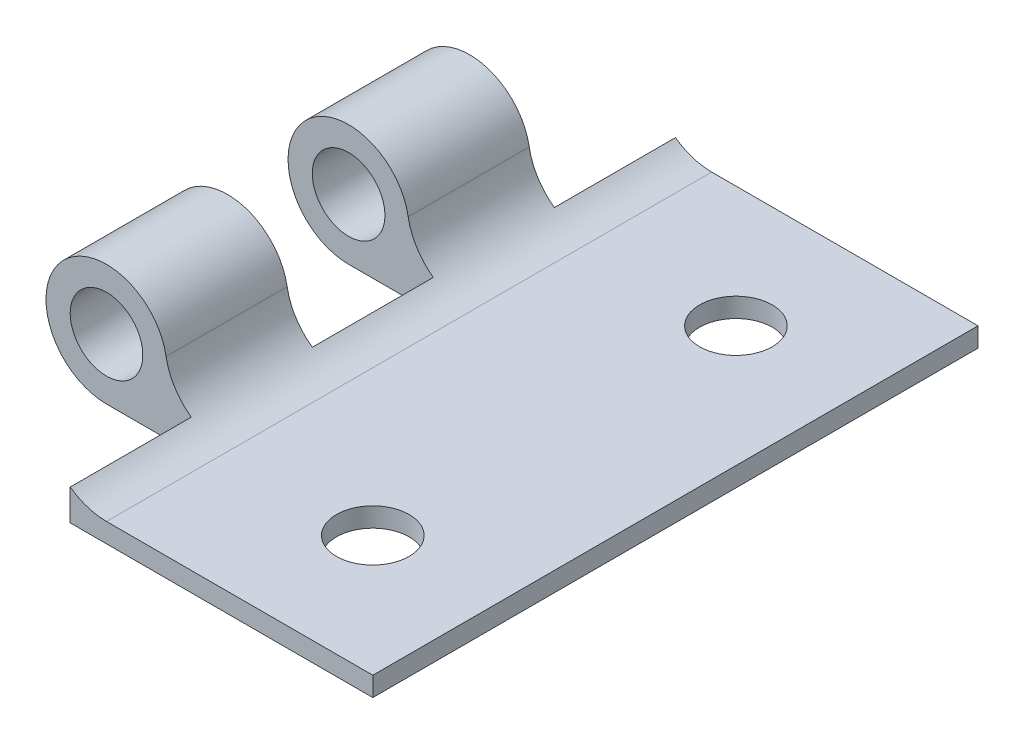
SolidWorks part; units mm, degrees
material "Aço cromo inoxidável"
ref_plane "Plano frontal" through (0, 0, 0) normal (0, 0, 1) x (1, 0, 0)
ref_plane "Plano superior" through (0, 0, 0) normal (0, 1, 0) x (1, 0, 0)
ref_plane "Plano direito" through (0, 0, 0) normal (1, 0, 0) x (0, 0, -1)
sketch "Esboço1" plane through (0, 0, 0) normal (0, 0, 1) x (1, 0, 0)
  line L0 (0, 0) -> (-16, 0)
  line L2 (-11, 0.8) -> (0, 0.8)
  line L3 (0, 0.8) -> (0, 0)
  arc A0 (-16, 0) -> (-14.2893, 4.323) centre (-16, 2.5) cw
  arc A1 (-14.2893, 4.323) -> (-13.5375, 2.9315) centre (-16, 2.5) cw
  arc A2 (-13.5375, 2.9315) -> (-11, 0.8) centre (-11, 3.3762) ccw
  circle A3 centre (-16, 2.5) radius 1.5
  dimension "D4" = 16
  dimension "D5" = 1
  dimension "D2" = 3
  dimension "D1" = 0.8
  dimension "D3" = 5
extrude "Ressalto-extrusão1" add sketch "Esboço1" along normal blind 25
sketch "Esboço2" plane through (0, 0, 0) normal (0, -1, 0) x (1, 0, 0)
  line L0 (-18.5, 25) -> (-18.5, 0) construction
  line L1 (-18.5, 0) -> (-12.5, 0)
  line L2 (-18.5, 0) -> (-18.5, 5)
  line L3 (-18.5, 5) -> (-12.5, 5)
  line L4 (-12.5, 0) -> (-12.5, 5)
  line L5 (0, 25) -> (0, 0) construction
  line L6 (-18.5, 0) -> (-13.5375, 0) construction
  line L7 (-18.5, 10) -> (-18.5, 15)
  line L8 (-18.5, 10) -> (-12.5, 10)
  line L9 (-12.5, 10) -> (-12.5, 15)
  line L10 (-18.5, 15) -> (-12.5, 15)
  line L11 (-18.5, 20) -> (-18.5, 25)
  line L12 (-18.5, 20) -> (-12.5, 20)
  line L13 (-12.5, 20) -> (-12.5, 25)
  line L14 (-18.5, 25) -> (-12.5, 25)
  line L15 (0, 12.5) -> (-9.0945, 12.5) construction
  line L16 (0, 25) -> (-11, 25) construction
  circle A0 centre (-5, 20) radius 1.5
  circle A1 centre (-5, 5) radius 1.5
  dimension "D5" = 3
  dimension "D1" = 5
  dimension "D2" = 3
  dimension "D3" = 5
  dimension "D4" = 6
  dimension "D6" = 5
  dimension "D7" = 5
extrude "Corte-extrusão2" cut sketch "Esboço2" against normal through all
